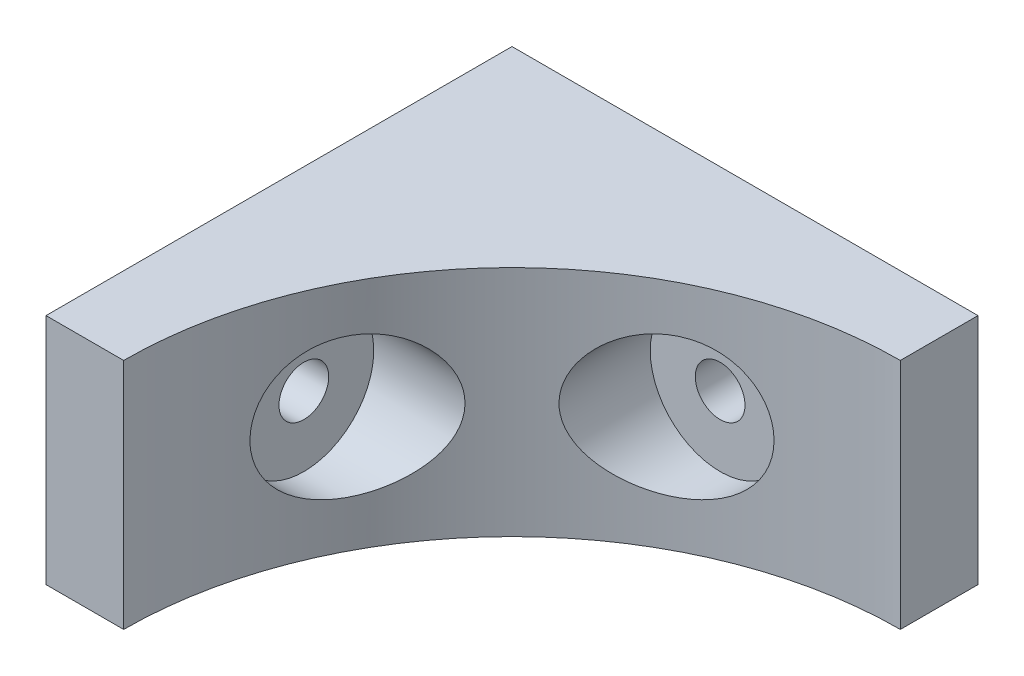
SolidWorks part; units mm, degrees
ref_plane "Front Plane" through (0, 0, 0) normal (0, 0, 1) x (1, 0, 0)
ref_plane "Top Plane" through (0, 0, 0) normal (0, 1, 0) x (1, 0, 0)
ref_plane "Right Plane" through (0, 0, 0) normal (1, 0, 0) x (0, 0, -1)
sketch "Sketch1" plane through (0, 0, 0) normal (0, 0, 1) x (1, 0, 0)
  line L0 (-1000, 0) -> (49000, 0) construction
  line L1 (-15, 7.5) -> (15, 7.5)
  line L2 (-15, 7.5) -> (-15, -7.5)
  line L3 (-15, -7.5) -> (15, -7.5)
  line L4 (15, 7.5) -> (15, -7.5)
  line L5 (-15, 7.5) -> (15, -7.5) construction
  line L6 (-15, -7.5) -> (15, 7.5) construction
  circle A0 centre (3.4, 0) radius 1.6
  point P0 (0, 0)
  dimension "D3" = 3.2
  dimension "D4" = 11.6
  dimension "D1" = 30
  dimension "D2" = 15
extrude "Boss-Extrude1" add sketch "Sketch1" along normal blind 5
sketch "Sketch2" plane through (0, 0, 5) normal (0, 0, 1) x (1, 0, 0)
  line L0 (-15, -7.5) -> (15, -7.5) construction
  line L1 (-15, 7.5) -> (-10, 7.5)
  line L2 (-15, 7.5) -> (-15, -7.5)
  line L3 (-15, -7.5) -> (-10, -7.5)
  line L4 (-10, 7.5) -> (-10, -7.5)
  dimension "D1" = 5
extrude "Boss-Extrude2" add sketch "Sketch2" along normal blind 25
sketch "Sketch3" plane through (-10, 0, 0) normal (1, 0, 0) x (0, 0, -1)
  line L0 (-1005, 0) -> (48995, 0) construction
  line L1 (-5, -7.5) -> (-5, 7.5) construction
  line L2 (-30, -7.5) -> (-30, 7.5) construction
  circle A0 centre (-18.4, 0) radius 1.6
  point P7 (-5, 0)
  dimension "D1" = 3.2
  dimension "D2" = 11.6
extrude "Cut-Extrude1" cut sketch "Sketch3" against normal up to next
fillet "Fillet1" radius 25 1 edges
sketch "Sketch4" plane through (-15, 0, 0) normal (-1, 0, 0) x (0, 0, 1)
  circle A0 centre (18.4, 0) radius 4.5
  dimension "D1" = 9
extrude "Cut-Extrude2" cut sketch "Sketch4" against normal through all from offset 5 offset against normal yes
sketch "Sketch5" plane through (0, 0, 0) normal (0, 0, -1) x (-1, 0, 0)
  circle A0 centre (-3.4, 0) radius 4.5
  dimension "D1" = 9
extrude "Cut-Extrude3" cut sketch "Sketch5" against normal through all from offset 5 offset against normal yes
